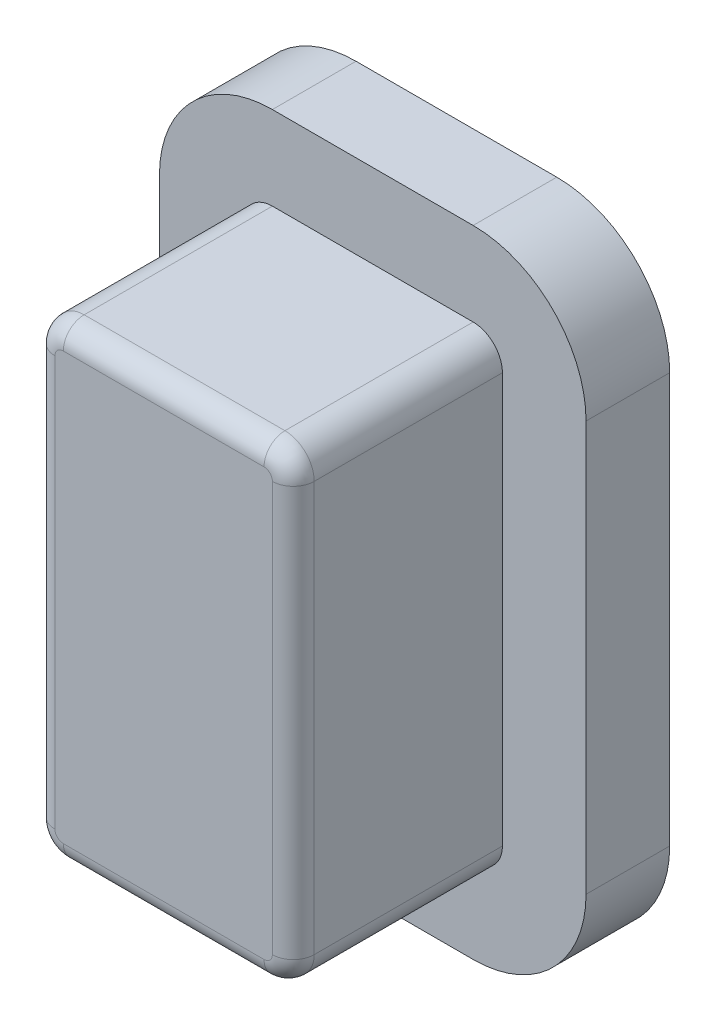
SolidWorks part; units mm, degrees
material "TPU 98A"
ref_plane "Alzado" through (0, 0, 0) normal (1, 0, 0) x (0, 1, 0)
ref_plane "Planta" through (0, 0, 0) normal (0, 0, 1) x (0, 1, 0)
ref_plane "Vista lateral" through (0, 0, 0) normal (0, 1, 0) x (-1, 0, 0)
sketch "Croquis1" plane through (0, 0, 0) normal (0, 0, 1) x (0, 1, 0)
  line L0 (-7.6, -2.4) -> (-7.6, 2.4)
  line L1 (-4.9, -3.1) -> (4.9, -3.1)
  line L2 (-5.6, -2.4) -> (-5.6, 2.4)
  line L3 (-4.9, 3.1) -> (4.9, 3.1)
  line L4 (5.6, -2.4) -> (5.6, 2.4)
  line L5 (-5.6, -3.1) -> (5.6, 3.1) construction
  line L6 (-5.6, 3.1) -> (5.6, -3.1) construction
  line L7 (-4.9, 5.1) -> (4.9, 5.1)
  line L8 (7.6, -2.4) -> (7.6, 2.4)
  line L9 (-4.9, -5.1) -> (4.9, -5.1)
  line L10 (-4.6, -2.1) -> (-4.6, 2.1)
  line L11 (-4.6, 2.1) -> (4.6, 2.1)
  line L12 (4.6, -2.1) -> (4.6, 2.1)
  line L13 (-4.6, -2.1) -> (4.6, -2.1)
  arc A0 (4.9, 3.1) -> (5.6, 2.4) centre (4.9, 2.4) cw
  arc A1 (4.9, -3.1) -> (5.6, -2.4) centre (4.9, -2.4) ccw
  arc A2 (-4.9, -3.1) -> (-5.6, -2.4) centre (-4.9, -2.4) cw
  arc A3 (-5.6, 2.4) -> (-4.9, 3.1) centre (-4.9, 2.4) cw
  arc A4 (-7.6, 2.4) -> (-4.9, 5.1) centre (-4.9, 2.4) cw
  arc A5 (4.9, 5.1) -> (7.6, 2.4) centre (4.9, 2.4) cw
  arc A6 (4.9, -5.1) -> (7.6, -2.4) centre (4.9, -2.4) ccw
  arc A7 (-4.9, -5.1) -> (-7.6, -2.4) centre (-4.9, -2.4) cw
  arc A8 (-4.6, 2.1) -> (-4.6, 2.1) centre (-4.6, 2.1) cw
  arc A9 (4.6, 2.1) -> (4.6, 2.1) centre (4.6, 2.1) cw
  arc A10 (4.6, -2.1) -> (4.6, -2.1) centre (4.6, -2.1) ccw
  arc A11 (-4.6, -2.1) -> (-4.6, -2.1) centre (-4.6, -2.1) cw
  circle A12 centre (0, 0) radius 1.6473
  point P0 (0, 0)
  point P18 (0, 1.6473)
  dimension "D1" = 0.7
  dimension "D2" = 11.2
  dimension "D3" = 6.2
  dimension "D6" = 0.4527
  dimension "D4" = 2
  dimension "D5" = 1
extrude "Saliente-Extruir1" add sketch "Croquis1" along normal blind 7 contours A3 L2 A2 L1 A1 L4 A0 L3 L13 L10 L11 L12 region at (2.8045, -5.3045, 0)
extrude "Saliente-Extruir2" add sketch "Croquis1<4>" along normal blind 2 contours A7 L9 A6 L8 A5 L7 A4 L0 L2 A3 L3 A0 L4 A1 L1 A2 region at (0, -7.4169, 0)
sketch "Croquis1<4>" plane through (0, 0, 0) normal (0, 0, 1) x (0, 1, 0) same geometry as "Croquis1"
extrude "Saliente-Extruir3" add sketch "Croquis1<5>" against normal blind 1 from surface contours L10 L13 L12 L11 region at (0, -4.4989, 0) starting at face at (0, 0, 7)
sketch "Croquis1<5>" plane through (0, 0, 0) normal (0, 0, 1) x (0, 1, 0) same geometry as "Croquis1"
extrude "Saliente-Extruir4" add sketch "Croquis1<6>" against normal blind 7 from surface contours A12 region at (0, 0, 0) starting at face at (0, 0, 7)
sketch "Croquis1<6>" plane through (0, 0, 0) normal (0, 0, 1) x (0, 1, 0) same geometry as "Croquis1"
sketch "Croquis2" plane through (0, 0, 0) normal (0, 0, -1) x (1, 0, 0)
  line L1 (-3.5, -3.5) -> (3.5, -3.5)
  line L2 (-3.5, -3.5) -> (-3.5, 3.5)
  line L3 (-3.5, 3.5) -> (3.5, 3.5)
  line L4 (3.5, -3.5) -> (3.5, 3.5)
  line L5 (-3.5, -3.5) -> (3.5, 3.5) construction
  line L6 (-3.5, 3.5) -> (3.5, -3.5) construction
  circle A0 centre (0, 0) radius 1.6473 construction
  circle A1 centre (0, 0) radius 1.6473
  point P0 (0, 0)
  line M5 (2.1, 4.6) -> (2.1, -4.6)
  line M7 (-2.1, -4.6) -> (-2.1, 4.6)
  dimension "D1" = 7
extrude "Cortar-Extruir1" cut sketch "Croquis2" against normal blind 1.3 contours L3 L1 A1 M7 M5 | L3 L2 L1 M7 | L1 L4 L3 M5 region at (-2.8, 0, 0) region at (-2.0184, 0, 0) region at (2.8, 0, 0)
fillet "Redondeo1" radius 0.5 8 edges at (-3.1, 0, 7) (-2.895, 5.395, 7) (0, 5.6, 7) (2.895, 5.395, 7) (3.1, 0, 7) (2.895, -5.395, 7) (0, -5.6, 7) (-2.895, -5.395, 7)
